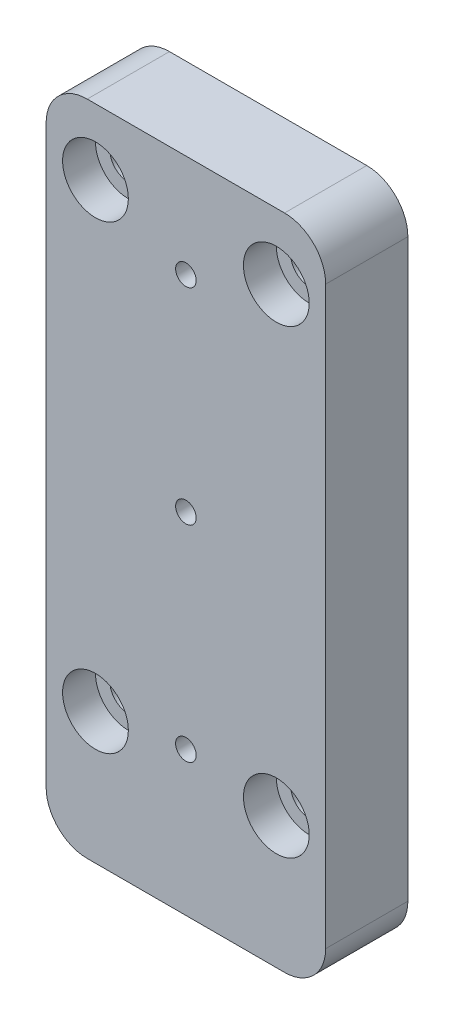
SolidWorks part; units mm, degrees
ref_plane "Front" through (0, 0, 0) normal (0, 0, 1) x (1, 0, 0)
ref_plane "Top" through (0, 0, 0) normal (0, 1, 0) x (1, 0, 0)
ref_plane "Right" through (0, 0, 0) normal (1, 0, 0) x (0, 0, -1)
sketch "Esquisse1" plane through (0, 0, 0) normal (0, 0, 1) x (1, 0, 0)
  line L1 (0, 0) -> (34, 0)
  line L2 (0, 0) -> (0, 80)
  line L3 (0, 80) -> (34, 80)
  line L4 (34, 0) -> (34, 80)
  dimension "D1" = 34
  dimension "D2" = 80
extrude "Boss.-Extru.1" add sketch "Esquisse1" along normal blind 10
sketch "Esquisse2" plane through (0, 0, 10) normal (0, 0, 1) x (1, 0, 0)
  line L0 (17, 0) -> (17, 80) construction
  line L1 (0, 0) -> (34, 0) construction
  line L2 (34, 80) -> (0, 80) construction
  circle A0 centre (17, 17.5) radius 1.25
  circle A1 centre (17, 42.5) radius 1.25
  circle A2 centre (17, 67.5) radius 1.25
  circle A3 centre (17, 92.5) radius 1.25
  circle A4 centre (17, 117.5) radius 1.25
  circle A5 centre (17, 142.5) radius 1.25
  circle A6 centre (17, 167.5) radius 1.25
  circle A7 centre (17, 192.5) radius 1.25
  dimension "D1" = 17.5
  dimension "D2" = 2.5
  dimension "D4" = 25
  dimension "D3" = 8
extrude "Enlèv. mat.-Extru.1" cut sketch "Esquisse2" against normal through all both and the other way through all
sketch "Esquisse3" plane through (0, 0, 10) normal (0, 0, 1) x (1, 0, 0)
  line L0 (17, 0) -> (17, 80) construction
  line L1 (0, 0) -> (34, 0) construction
  line L2 (34, 80) -> (0, 80) construction
  line L3 (0, 44) -> (34, 44) construction
  line L5 (34, 0) -> (34, 80) construction
  line L6 (0, 80) -> (0, 0) construction
  circle A0 centre (6, 16) radius 2.25
  circle A1 centre (28, 16) radius 2.25
  circle A2 centre (28, 72) radius 2.25
  circle A3 centre (6, 72) radius 2.25
  dimension "D1" = 22
  dimension "D2" = 16
  dimension "D3" = 4.5
  dimension "D4" = 56
extrude "Enlèv. mat.-Extru.2" cut sketch "Esquisse3" against normal through all both and the other way through all
sketch "Esquisse4" plane through (0, 0, 10) normal (0, 0, 1) x (1, 0, 0)
  circle A0 centre (6, 16) radius 4
  circle A1 centre (28, 16) radius 4
  circle A2 centre (6, 72) radius 4
  circle A3 centre (28, 72) radius 4
  dimension "D1" = 8
extrude "Enlèv. mat.-Extru.3" cut sketch "Esquisse4" against normal blind 4
fillet "Congé1" radius 5 4 edges at (0, 80, 5) (34, 80, 5) (34, 0, 5) (0, 0, 5)
